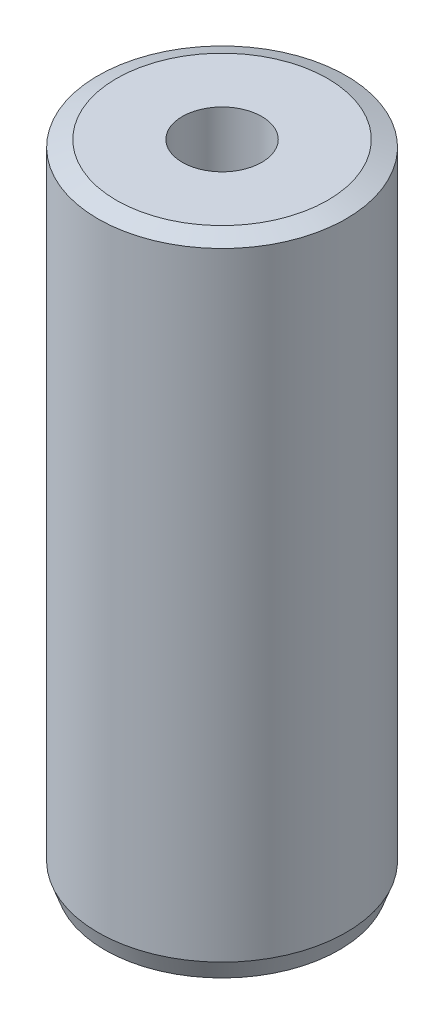
SolidWorks part; units mm, degrees
ref_plane "Front Plane" through (0, 0, 0) normal (0, 0, 1) x (1, 0, 0)
ref_plane "Top Plane" through (0, 0, 0) normal (0, 1, 0) x (1, 0, 0)
ref_plane "Right Plane" through (0, 0, 0) normal (1, 0, 0) x (0, 0, -1)
sketch "Sketch1" plane through (0, 0, 0) normal (0, 1, 0) x (1, 0, 0)
  circle A0 centre (0, 0) radius 12.5
  dimension "SHAFT_OD" = 25
extrude "Boss-Extrude1" add sketch "Sketch1" along normal blind 64.8104
sketch "Sketch2" plane through (0, 0, 0) normal (0, 1, 0) x (1, 0, 0)
  circle A0 centre (0, 0) radius 4.0051
  dimension "BORE_D" = 8.0102
extrude "Cut-Extrude1" cut sketch "Sketch2" along normal through all
chamfer "Chamfer1" distance 0.6834 angle 69.863 2 edges at (0, 64.8104, 12.5) (0, 0, 12.5) first distance on face at (0, 64.8104, 12.5) first distance on face at (0, 0, 4.0051)
